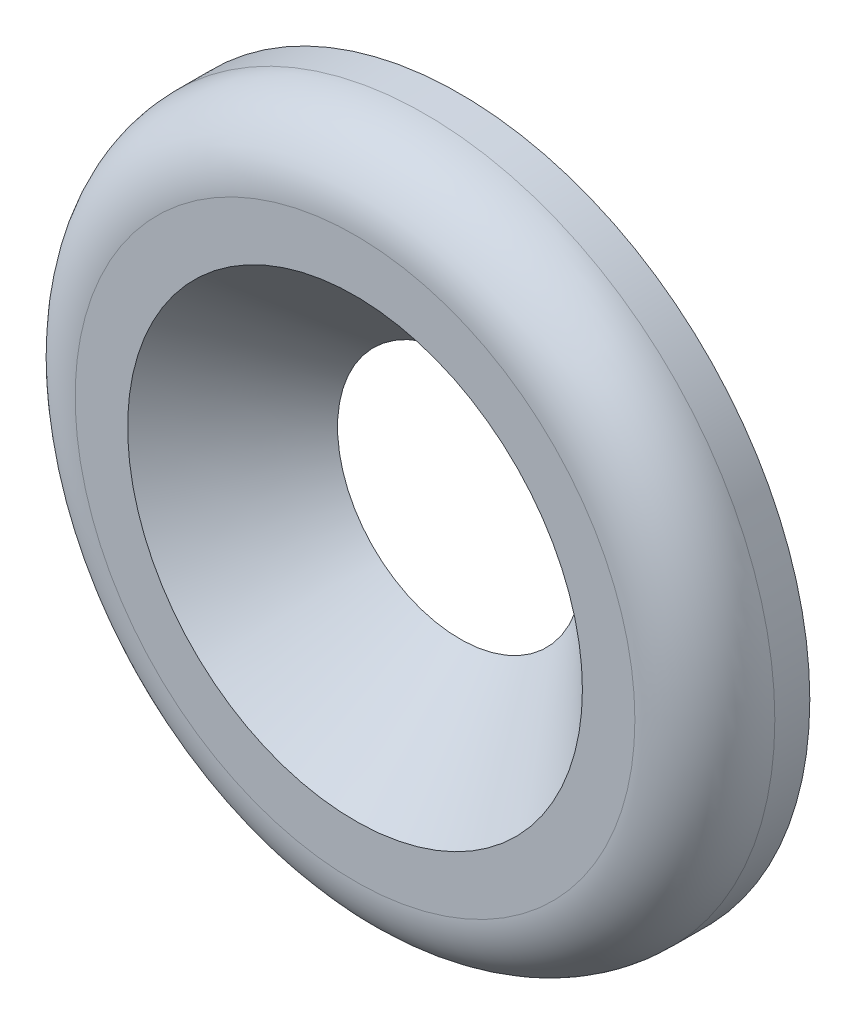
SolidWorks part; units mm, degrees
ref_plane "Front Plane" through (0, 0, 0) normal (0, 0, 1) x (1, 0, 0)
ref_plane "Top Plane" through (0, 0, 0) normal (0, 1, 0) x (1, 0, 0)
ref_plane "Right Plane" through (0, 0, 0) normal (1, 0, 0) x (0, 0, -1)
sketch "Sketch1" plane through (0, 0, 0) normal (0, 0, 1) x (1, 0, 0)
  circle A0 centre (0, 0) radius 5
  dimension "D1" = 10
extrude "Boss-Extrude1" add sketch "Sketch1" along normal blind 1.5
sketch "Sketch2" plane through (0, 0, 0) normal (0, 0, 1) x (1, 0, 0)
  circle A0 centre (0, 0) radius 1.75
  dimension "D1" = 3.5
extrude "Cut-Extrude1" cut sketch "Sketch2" along normal through all
chamfer "Chamfer1" distance 1.5 angle 45 1 edges at (1.75, 0, 1.5)
fillet "Fillet1" radius 1 1 edges at (5, 0, 1.5)
